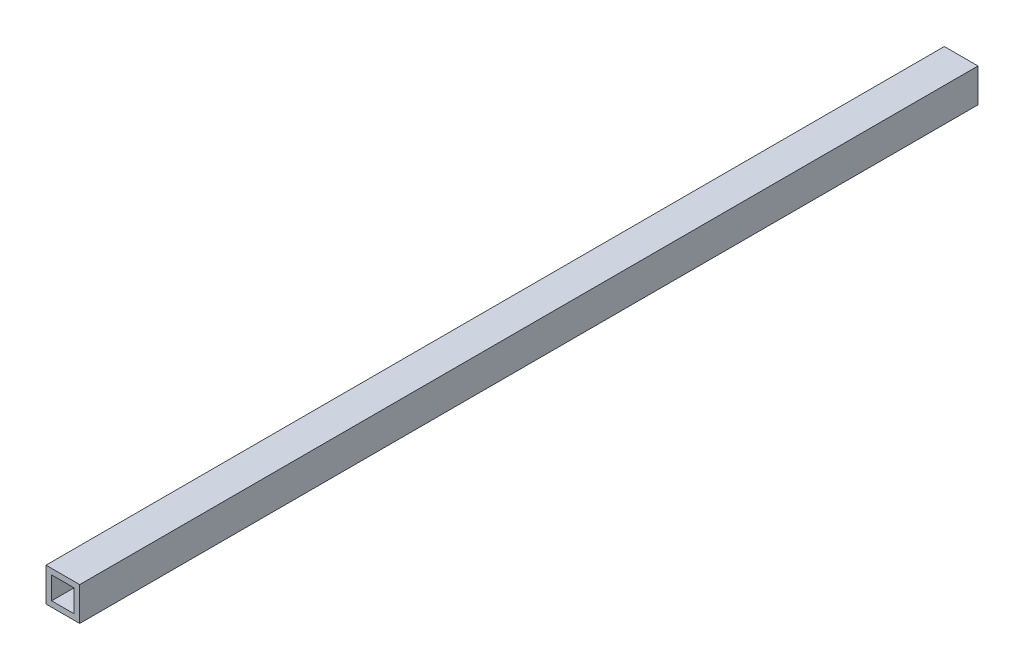
SolidWorks part; units mm, degrees
ref_plane "Front Plane" through (0, 0, 0) normal (0, 0, 1) x (1, 0, 0)
ref_plane "Top Plane" through (0, 0, 0) normal (0, 1, 0) x (1, 0, 0)
ref_plane "Right Plane" through (0, 0, 0) normal (1, 0, 0) x (0, 0, -1)
sketch "Sketch1" plane through (0, 0, 0) normal (0, 0, 1) x (1, 0, 0)
  line L1 (-9.525, -9.525) -> (9.525, -9.525)
  line L2 (-9.525, -9.525) -> (-9.525, 9.525)
  line L3 (-9.525, 9.525) -> (9.525, 9.525)
  line L4 (9.525, -9.525) -> (9.525, 9.525)
  line L5 (-9.525, -9.525) -> (9.525, 9.525) construction
  line L6 (-9.525, 9.525) -> (9.525, -9.525) construction
  point P0 (0, 0)
  dimension "D1" = 19.05
  dimension "D2" = 19.05
extrude "Boss-Extrude1" add sketch "Sketch1" against normal blind 508
sketch "Sketch2" plane through (0, 0, 0) normal (0, 0, 1) x (1, 0, 0)
  line L1 (-6.35, -6.35) -> (6.35, -6.35)
  line L2 (-6.35, -6.35) -> (-6.35, 6.35)
  line L3 (-6.35, 6.35) -> (6.35, 6.35)
  line L4 (6.35, -6.35) -> (6.35, 6.35)
  line L5 (-6.35, -6.35) -> (6.35, 6.35) construction
  line L6 (-6.35, 6.35) -> (6.35, -6.35) construction
  point P0 (0, 0)
  dimension "D1" = 12.7
  dimension "D2" = 12.7
extrude "Cut-Extrude1" cut sketch "Sketch2" against normal up to next
equation "\"D2@Sketch1\"=\"D1@Sketch1\""
equation "\"D2@Sketch2\"=\"D1@Sketch2\""
